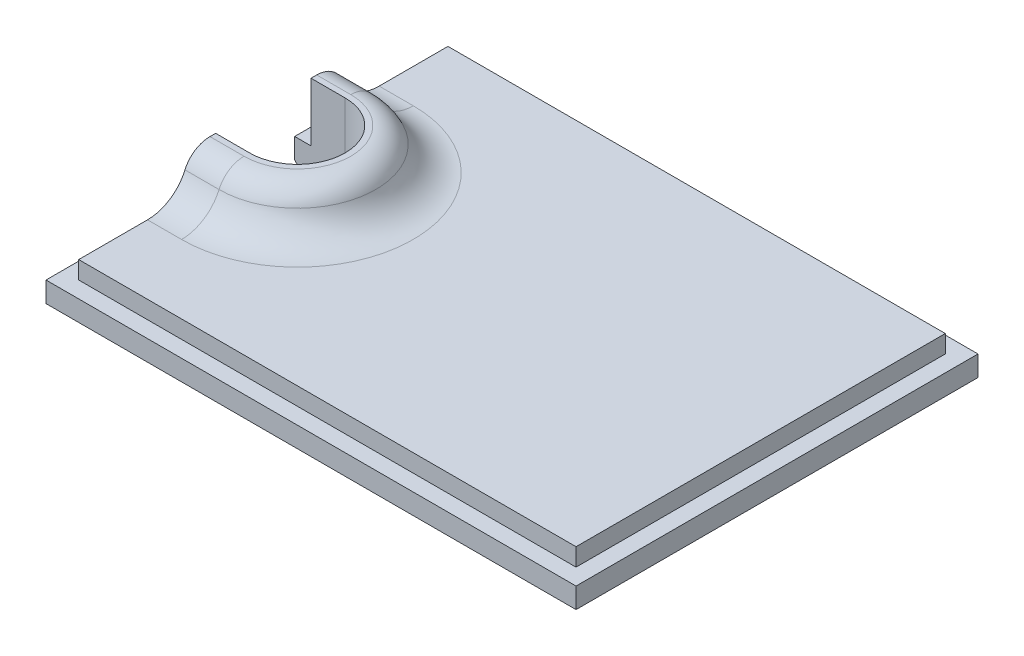
SolidWorks part; units mm, degrees
ref_plane "Front Plane" through (0, 0, 0) normal (0, 0, 1) x (1, 0, 0)
ref_plane "Top Plane" through (0, 0, 0) normal (0, 1, 0) x (1, 0, 0)
ref_plane "Right Plane" through (0, 0, 0) normal (1, 0, 0) x (0, 0, -1)
sketch "Sketch1" plane through (0, 0, 0) normal (0, 1, 0) x (1, 0, 0)
  line L0 (-19.45, 14.75) -> (-19.45, 3.5)
  line L1 (-19.45, -14.75) -> (19.45, -14.75)
  line L2 (19.45, -14.75) -> (19.45, 14.75)
  line L3 (19.45, 14.75) -> (-19.45, 14.75)
  line L4 (18.25, 13.55) -> (-18.25, 13.55)
  line L5 (-18.25, 13.55) -> (-18.25, 3.5)
  line L6 (-18.25, -13.55) -> (18.25, -13.55)
  line L7 (18.25, -13.55) -> (18.25, 13.55)
  line L8 (-18.25, 13.55) -> (0, 0) construction
  line L9 (0, 0) -> (18.25, -13.55) construction
  line L10 (0, 0) -> (18.25, 13.55) construction
  line L11 (0, 0) -> (-18.25, -13.55) construction
  line L12 (-15.75, 5.5) -> (-18.25, 5.5)
  line L13 (-18.25, 5.5) -> (-19.45, 5.5)
  line L14 (-15.75, 3.5) -> (-18.25, 3.5)
  line L15 (-18.25, 3.5) -> (-19.45, 3.5)
  line L16 (-15.75, -3.5) -> (-18.25, -3.5)
  line L17 (-18.25, -3.5) -> (-19.45, -3.5)
  line L18 (-15.75, -5.5) -> (-18.25, -5.5)
  line L19 (-18.25, -5.5) -> (-19.45, -5.5)
  line L20 (-19.45, -3.5) -> (-19.45, -14.75)
  line L21 (-19.45, 14.75) -> (-19.45, -14.75) construction
  line L22 (-18.25, -3.5) -> (-18.25, -13.55)
  line L23 (-18.25, 13.55) -> (-18.25, -13.55) construction
  line L24 (-15.75, 0) -> (-15.75, 13.55) construction
  line L25 (-15.75, 0) -> (-15.75, -13.55) construction
  arc A0 (-15.75, 3.5) -> (-15.75, -3.5) centre (-15.75, 0) cw
  arc A1 (-15.75, 5.5) -> (-15.75, -5.5) centre (-15.75, 0) cw
  arc A2 (-17.6698, 2.9265) -> (-15.75, -3.5) centre (-15.75, 0) cw construction
  arc A3 (-18.7669, 4.5987) -> (-15.75, -5.5) centre (-15.75, 0) cw construction
  dimension "D4" = 3.5
  dimension "D6" = 2
  dimension "D1" = 29.5
  dimension "D2" = 38.9
  dimension "D7" = 2.5
  dimension "D3" = 1.2
extrude "Boss-Extrude1" add sketch "Sketch1" along normal blind 1 contours L12 A1 L18 L5 L6 L7 L4 | A1 L12 L5 L14 A0 L16 L18 | L19 L5 L17 L0 | L15 L5 L13 L0 | L5 L19 L0 L1 L2 L3 L13 L4 L7 L6 | L17 L20 L1 L2 L3 L0 L15 L14 A0 L16 | L4 L5 L6 L7 region at (0, 0, -14.2618) region at (-18.85, 0, -4.5) region at (-17, 0, -5.364) region at (1.2088, 0, 0)
extrude "Boss-Extrude2" add sketch "Sketch1<5>" along normal blind 1.6 from surface contours L5 A1 L6 L7 L4 | A1 L5 A0 | A1 L0 A0 L5 | L0 A1 L5 L4 L7 L6 L1 L2 L3 | A1 L5 A0 L0 | L5 L0 | L5 L0 | L22 L17 L20 L19 region at (0, 0, -14.2618) region at (-18.85, 0, -4.5) region at (-17, 0, -5.364) region at (1.2088, 0, 0) region at (-18.85, 0, 4.5) starting at face at (-8.3625, 1, 0)
sketch "Sketch1<5>" plane through (0, 0, 0) normal (0, 1, 0) x (1, 0, 0) same geometry as "Sketch1"
extrude "Boss-Extrude3" add sketch "Sketch1<6>" along normal blind 1.3 from surface contours L5 A1 L6 L7 L4 | A1 L5 A0 region at (-17, 0, -5.364) region at (1.2088, 0, 0) starting at face at (-8.3625, 2.6, 0)
sketch "Sketch1<6>" plane through (0, 0, 0) normal (0, 1, 0) x (1, 0, 0) same geometry as "Sketch1"
extrude "Boss-Extrude4" add sketch "Sketch1<8>" along normal blind 3 from surface contours A1 L5 A0 region at (-17, 0, -5.364) starting at face at (-8.0625, 3.9, 0)
sketch "Sketch1<8>" plane through (0, 0, 0) normal (0, 1, 0) x (1, 0, 0) same geometry as "Sketch1"
chamfer "Chamfer1" distance 1.1 angle 45 5 edges at (0, 0, -14.75) (19.45, 0, 0) (0, 0, 14.75) (-19.45, 0, -9.125) (-19.45, 0, 9.125)
fillet "Fillet1" radius 3 3 edges at (-17, 3.9, 5.5) (-17, 3.9, -5.5) (-10.25, 3.9, 0)
fillet "Fillet2" radius 2 3 edges at (-17, 6.9, -5.5) (-17, 6.9, 5.5) (-10.25, 6.9, 0)
